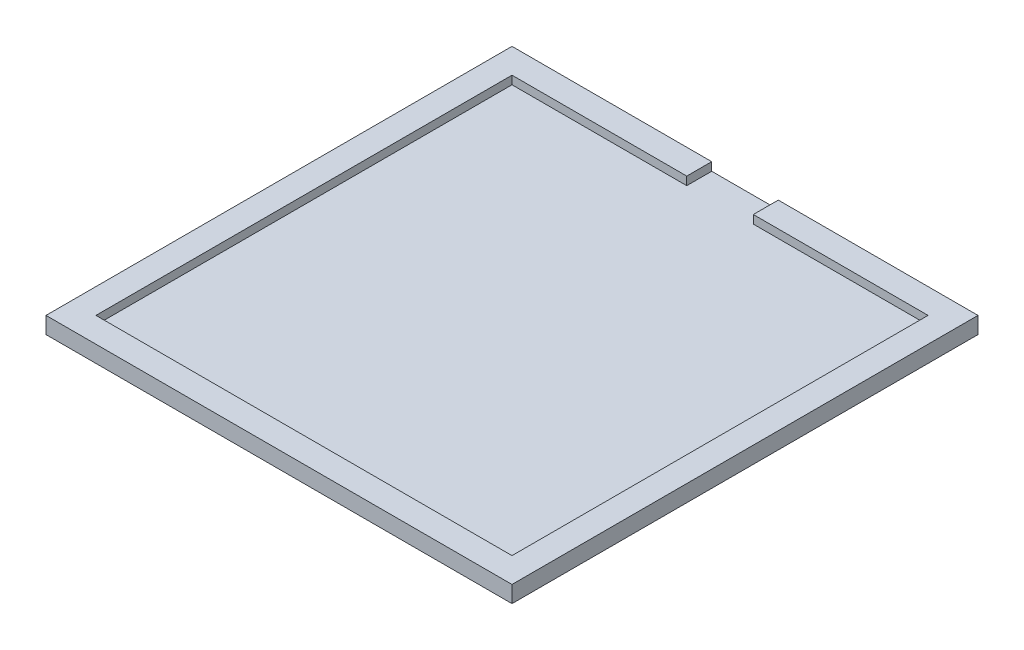
SolidWorks part; units mm, degrees
ref_plane "Front Plane" through (0, 0, 0) normal (0, 0, 1) x (1, 0, 0)
ref_plane "Top Plane" through (0, 0, 0) normal (0, 1, 0) x (1, 0, 0)
ref_plane "Right Plane" through (0, 0, 0) normal (1, 0, 0) x (0, 0, -1)
sketch "Sketch1" plane through (0, 0, 0) normal (0, 1, 0) x (1, 0, 0)
  line L0 (-28, 28) -> (-28, -28)
  line L1 (-25, 25) -> (25, 25)
  line L2 (-25, 25) -> (-25, -25)
  line L3 (-25, -25) -> (25, -25)
  line L4 (25, 25) -> (25, -25)
  line L5 (-25, 25) -> (25, -25) construction
  line L6 (-25, -25) -> (25, 25) construction
  line L7 (-28, -28) -> (28, -28)
  line L8 (28, 28) -> (28, -28)
  line L9 (-28, 28) -> (28, 28)
  point P0 (0, 0)
  dimension "D1" = 50
  dimension "D2" = 50
  dimension "D3" = 3
extrude "Boss-Extrude1" add sketch "Sketch1" along normal blind 1 contours L4 L1 L2 L3 | L9 L0 L7 L8 L1 L4 L3 L2 region at (0, 0, -27.208) region at (0, 0, 0)
extrude "Boss-Extrude2" add sketch "Sketch1<3>" along normal blind 2 contours L9 L0 L7 L8 L1 L4 L3 L2 region at (0, 0, -27.208)
sketch "Sketch1<3>" plane through (0, 0, 0) normal (0, 1, 0) x (1, 0, 0) same geometry as "Sketch1"
sketch "Sketch2" plane through (0, 2, 0) normal (0, 1, 0) x (1, 0, 0)
  line L1 (4, 41.6755) -> (-4, 41.6755)
  line L2 (4, 41.6755) -> (4, 22.2391)
  line L3 (4, 22.2391) -> (-4, 22.2391)
  line L4 (-4, 41.6755) -> (-4, 22.2391)
  line L5 (4, 41.6755) -> (-4, 22.2391) construction
  line L6 (4, 22.2391) -> (-4, 41.6755) construction
  point P0 (0, 31.9573)
  point P7 (0, 0)
  dimension "D1" = 8
extrude "Cut-Extrude1" cut sketch "Sketch2" against normal blind 1
